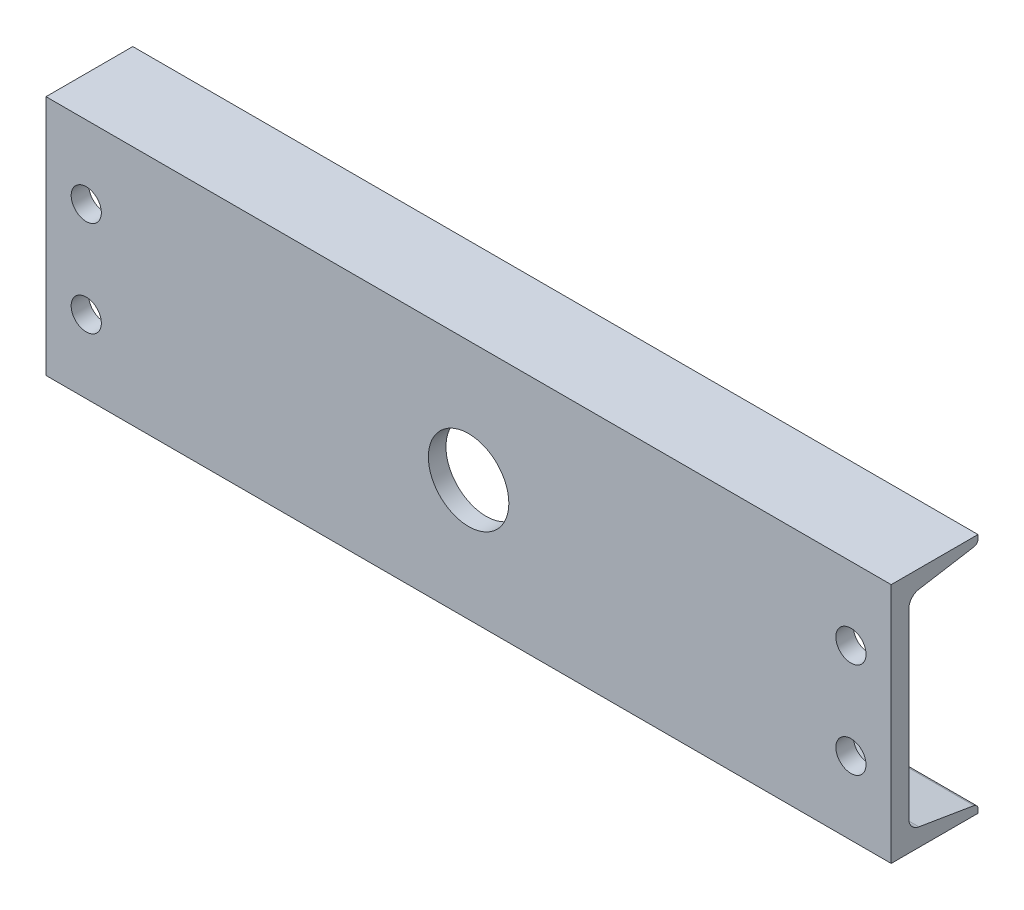
SolidWorks part; units mm, degrees
ref_plane "Front Plane" through (0, 0, 0) normal (0, 0, 1) x (1, 0, 0)
ref_plane "Top Plane" through (0, 0, 0) normal (0, 1, 0) x (1, 0, 0)
ref_plane "Right Plane" through (0, 0, 0) normal (1, 0, 0) x (0, 0, -1)
sketch "Sketch1" plane through (0, 0, 0) normal (1, 0, 0) x (0, 0, -1)
  line L0 (-27.3939, -76.2) -> (-27.3939, 76.2)
  line L1 (-27.3939, 76.2) -> (27.3939, 76.2)
  line L2 (-27.3939, -76.2) -> (27.3939, -76.2)
  line L3 (4.3561, -67.4878) -> (-21.0439, -67.4878) construction
  line L4 (-16.2941, 57.3918) -> (-16.2941, -57.3918)
  line L5 (27.3939, 76.2) -> (27.3939, 73.7107)
  line L6 (27.3939, -76.2) -> (27.3939, -73.7107)
  line L7 (-9.9269, 64.9081) -> (24.847, 70.7042)
  line L8 (-9.9269, -64.9081) -> (24.847, -70.7042)
  arc A0 (-16.2941, -57.3918) -> (-9.9269, -64.9081) centre (-8.6741, -57.3918) ccw
  arc A1 (-16.2941, 57.3918) -> (-9.9269, 64.9081) centre (-8.6741, 57.3918) cw
  arc A2 (27.3939, 73.7107) -> (24.847, 70.7042) centre (24.3459, 73.7107) cw
  arc A3 (27.3939, -73.7107) -> (24.847, -70.7042) centre (24.3459, -73.7107) ccw
extrude "Boss-Extrude1" add sketch "Sketch1" along normal mid plane 533.4
sketch "Sketch2" plane through (0, 0, 27.3939) normal (0, 0, 1) x (1, 0, 0)
  circle A1 centre (0, 0) radius 25.4
  dimension "D1" = 50.8
extrude "Cut-Extrude1" cut sketch "Sketch2" against normal up to next
sketch "Sketch3" plane through (0, 0, 27.3939) normal (0, 0, 1) x (1, 0, 0)
  line L0 (266.7, 76.2) -> (-266.7, 76.2) construction
  line L1 (-266.7, 76.2) -> (-266.7, -76.2) construction
  line L2 (0, 76.2) -> (0, -76.2) construction
  line L3 (266.7, -76.2) -> (-266.7, -76.2) construction
  line L4 (-266.7, 0) -> (266.7, 0) construction
  line L5 (266.7, 76.2) -> (266.7, -76.2) construction
  circle A0 centre (-241.3, 30.1625) radius 9.525
  circle A1 centre (241.3, 30.1625) radius 9.525
  circle A2 centre (241.3, -30.1625) radius 9.525
  circle A3 centre (-241.3, -30.1625) radius 9.525
  dimension "D3" = 19.05
  dimension "D1" = 46.0375
  dimension "D2" = 25.4
extrude "Cut-Extrude2" cut sketch "Sketch3" against normal up to next
